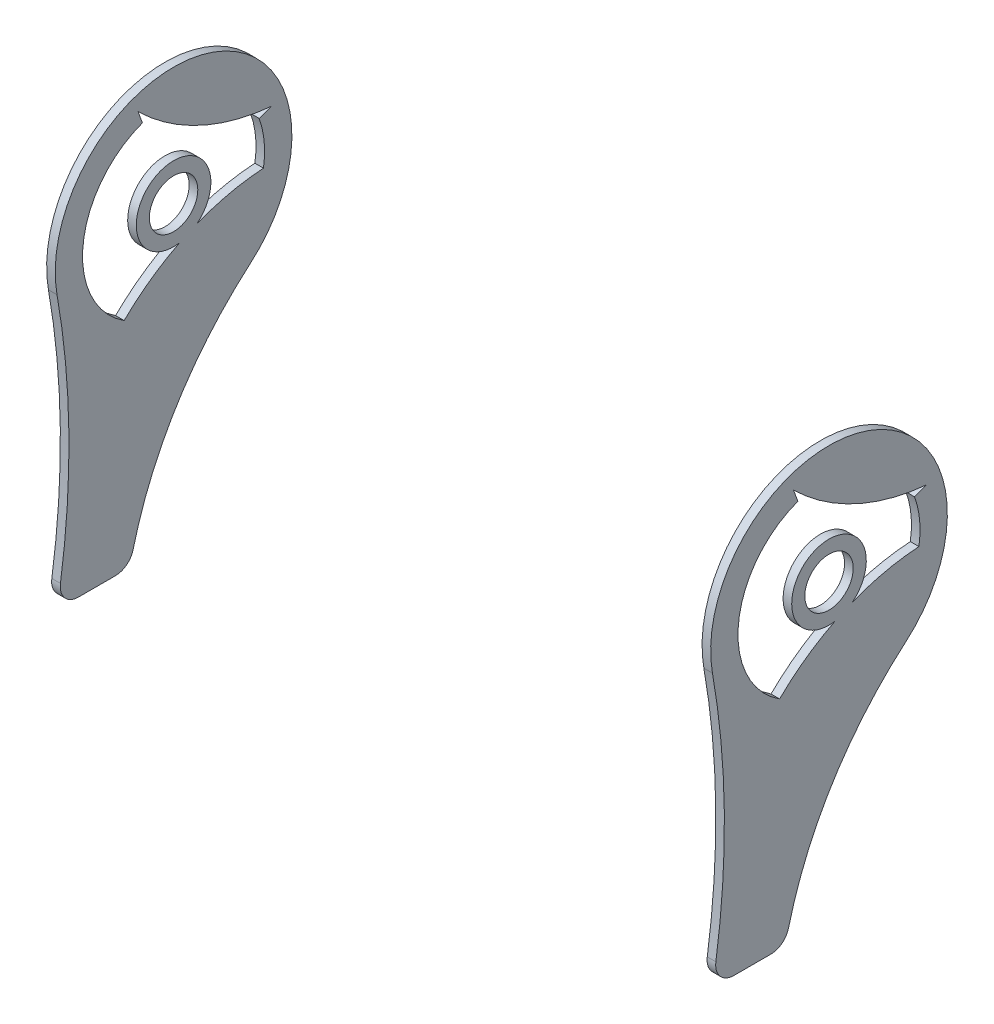
SolidWorks part; units mm, degrees
material "Ti-6Al-4VSolution treated and aged (SS)"
ref_plane "Front Plane" through (0, 0, 0) normal (0, 0, 1) x (1, 0, 0)
ref_plane "Top Plane" through (0, 0, 0) normal (0, 1, 0) x (1, 0, 0)
ref_plane "Right Plane" through (0, 0, 0) normal (1, 0, 0) x (0, 0, -1)
sketch "Sketch1" plane through (56.4, 0, 0) normal (1, 0, 0) x (0, 0, -1)
  line L0 (-191.22, -24.13) -> (-178.52, -24.13)
  line L1 (-191.22, -24.13) -> (-127.7785, -35.3164) construction
  arc A0 (-157.4774, 11.3114) -> (-191.2234, 23.4009) centre (-170.9, 26.9875) ccw
  arc A1 (-189.47, 35.991) -> (-191.2234, 23.4009) centre (-170.9, 26.9875) ccw construction
  circle A2 centre (-170.9, 26.9875) radius 4.2228
  arc A3 (-191.2234, 23.4009) -> (-191.22, -24.13) centre (-325.9451, -0.3743) cw
  arc A4 (-191.22, -24.13) -> (-191.2234, 23.4009) centre (-325.9451, -0.3743) ccw construction
  arc A5 (-178.52, -24.13) -> (-157.4774, 11.3114) centre (-115.7344, -37.4401) cw
  dimension "D1" = 8.4455
extrude "Boss-Extrude1" add sketch "Sketch1" along normal blind 1.5
sketch "Sketch2" plane through (57.9, 0, 0) normal (1, 0, 0) x (0, 0, -1)
  line L0 (-177.0897, 43.9936) -> (-176.3296, 41.9051)
  line L1 (-153.8939, 33.1772) -> (-155.9824, 32.4171)
  line L4 (-170.9, 26.9875) -> (-170.9, 53.9132) construction
  arc A0 (-166.8176, 21.9216) -> (-169.8471, 20.5672) centre (-170.9, 26.9875) ccw
  arc A1 (-176.3296, 41.9051) -> (-155.9824, 32.4171) centre (-170.9, 26.9875) ccw
  arc A2 (-157.4774, 11.3114) -> (-191.2234, 23.4009) centre (-170.9, 26.9875) ccw construction
  arc A3 (-177.0897, 43.9936) -> (-153.8939, 33.1772) centre (-150.3255, 71.1097) ccw
  arc A4 (-179.5171, 13.6548) -> (-169.8471, 20.5672) centre (-152.7968, -13.5047) cw
  arc A5 (-171.8864, 42.8318) -> (-158.1285, 36.4164) centre (-170.9, 26.9875) cw construction
  arc A6 (-171.8864, 42.8318) -> (-158.1285, 36.4164) centre (-150.3255, 71.1097) ccw construction
  circle A7 centre (-170.9, 26.9875) radius 18.0975 construction
  circle A8 centre (-170.9, 26.9875) radius 6.2547 construction
  circle A9 centre (-170.9, 26.9875) radius 4.2228 construction
  arc A10 (-166.8176, 21.9216) -> (-155.2182, 24.5183) centre (-152.7968, -13.5047) cw
  dimension "D1" = 4.7625
  dimension "D2" = 2.54
  dimension "D3" = 2.54
  dimension "D5" = 38.1
  dimension "D6" = 38.1
  dimension "D7" = 2.032
  dimension "D4" = 20
extrude "Cut-Extrude1" cut sketch "Sketch2" against normal up to next and the other way through all contours A0 A10 A1 L1 A3 L0 A4 region at (57.9, 36.1739, 166.6163)
fillet "Fillet1" radius 3.175 2 edges at (57.15, -24.13, 178.52) (57.15, -24.13, 191.22)
mirror "Mirror2" about plane through (0, 0, 0) normal (1, 0, 0) of bodies 103 101
equation "\"weapon shaft threads\"= 5 / 16"
equation "\"D1@Sketch1\"=\"weapon shaft threads\" + .02in"
equation "\"D1@Boss-Extrude1\"=1.5mm"
